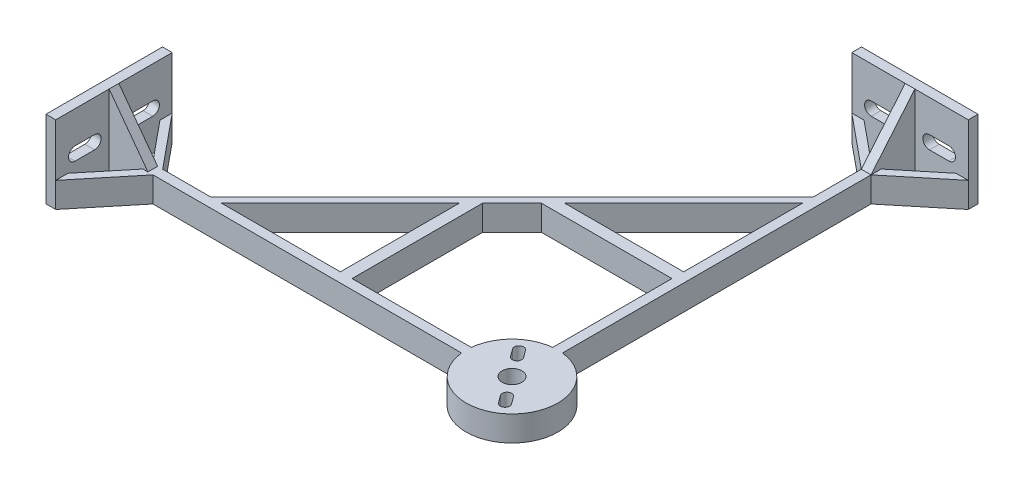
SolidWorks part; units mm, degrees
material "ABS"
ref_plane "Front Plane" through (0, 0, 0) normal (0, 0, 1) x (1, 0, 0)
ref_plane "Top Plane" through (0, 0, 0) normal (0, 1, 0) x (1, 0, 0)
ref_plane "Right Plane" through (0, 0, 0) normal (1, 0, 0) x (0, 0, -1)
sketch "Sketch1" plane through (0, 0, 0) normal (0, 1, 0) x (1, 0, 0)
  line L0 (-1.5875, 14.9158) -> (-1.5875, 130.175)
  line L1 (1.5875, 130.175) -> (1.5875, 14.9158)
  line L2 (-1.5875, 130.175) -> (1.5875, 130.175)
  line L4 (-14.9158, -1.5875) -> (-130.175, -1.5875)
  line L5 (-130.175, -1.5875) -> (-130.175, 1.5875)
  line L8 (-130.175, 1.5875) -> (-14.9158, 1.5875)
  line L9 (0, 0) -> (-130.175, 0) construction
  line L11 (0, 0) -> (0, 146.05) construction
  circle A0 centre (0, 0) radius 15
  point P19 (0, 0)
  point P21 (0, 0)
  dimension "D1" = 30
  dimension "D2" = 3.175
  dimension "D4" = 1.5875
  dimension "D3" = 2
  dimension "D5" = 130.175
extrude "Boss-Extrude2" add sketch "Sketch1" along normal blind 8.255 contours A0
extrude "Boss-Extrude3" add sketch "Sketch1<6>" along normal blind 8.255 contours L4 A0 | A0 | A0 region at (0, 0, -72.5735) region at (-72.5735, 0, 0)
sketch "Sketch1<6>" plane through (0, 0, 0) normal (0, 1, 0) x (1, 0, 0) same geometry as "Sketch1"
sketch "Sketch5" plane through (0, 8.255, 0) normal (0, 1, 0) x (1, 0, 0)
  line L0 (0, 0) -> (130.175, 0) construction
  line L1 (0, 0) -> (0, -22.3627) construction
  line L2 (-6.4967, 8.7797) -> (0, 0) construction
  line L3 (-4.6836, 6.3296) -> (-6.4967, 8.7797) construction
  line L4 (-5.9087, 5.4231) -> (-7.7217, 7.8732)
  line L5 (-3.4586, 7.2361) -> (-5.2716, 9.6862)
  line L6 (0, 0) -> (1.0099, 0.7473) construction
  line L7 (4.6836, -6.3296) -> (6.4967, -8.7797) construction
  line L8 (3.4586, -7.2361) -> (5.2716, -9.6862)
  line L9 (5.9087, -5.4231) -> (7.7217, -7.8732)
  line L10 (-1.5875, 130.175) -> (1.5875, 130.175) construction
  arc A0 (3.4586, -7.2361) -> (5.9087, -5.4231) centre (4.6836, -6.3296) cw
  arc A1 (-5.9087, 5.4231) -> (-3.4586, 7.2361) centre (-4.6836, 6.3296) ccw
  arc A2 (-5.2716, 9.6862) -> (-7.7217, 7.8732) centre (-6.4967, 8.7797) ccw
  arc A3 (7.7217, -7.8732) -> (5.2716, -9.6862) centre (6.4967, -8.7797) cw
  circle A6 centre (0, 0) radius 3.25
  point P8 (-5.5901, 7.5546)
  point P17 (5.5901, -7.5546)
  point P18 (0, 0)
  dimension "D3" = 3.048
  dimension "D1" = 7.874
  dimension "D2" = 3.048
  dimension "D4" = 53.5
extrude "Cut-Extrude3" cut sketch "Sketch5" against normal blind 63.5
ref_axis "Axis1" through (0, 0, 0) along (0, 1, 0)
ref_plane "Plane1" through (0, 0, 0) normal (0, 0, 1) x (1, 0, 0)
ref_plane "Plane2" through (0, 0, 0) normal (1, 0, 0) x (0, 0, -1)
sketch "Sketch7" plane through (0, 0, 0) normal (1, 0, 0) x (0, 0, -1)
  line L1 (130.175, 0) -> (133.35, 0)
  line L2 (130.175, 0) -> (130.175, 25.4)
  line L3 (130.175, 25.4) -> (133.35, 25.4)
  line L4 (133.35, 0) -> (133.35, 25.4)
  dimension "D1" = 3.175
  dimension "D2" = 25.4
extrude "Boss-Extrude5" add sketch "Sketch7" along normal blind 19.05 and the other way blind 19.05
sketch "Sketch8" plane through (-19.05, 0, 0) normal (-1, 0, 0) x (0, 0, 1)
  line L1 (-133.35, 0) -> (-130.175, 0)
  line L2 (-133.35, 0) -> (-133.35, 25.4)
  line L3 (-133.35, 25.4) -> (-130.175, 25.4)
  line L4 (-130.175, 0) -> (-130.175, 25.4)
sketch "Sketch12" plane through (0, 0, -133.35) normal (0, 0, -1) x (-1, 0, 0)
  line L0 (-19.05, 12.7) -> (19.05, 12.7) construction
  line L1 (-19.05, 0) -> (-19.05, 25.4) construction
  line L2 (19.05, 0) -> (19.05, 25.4) construction
  line L3 (-6.35, 12.7) -> (-12.7, 12.7) construction
  line L4 (-6.35, 10.541) -> (-12.7, 10.541)
  line L5 (-6.35, 14.859) -> (-12.7, 14.859)
  line L6 (6.35, 12.7) -> (12.7, 12.7) construction
  line L7 (6.35, 14.859) -> (12.7, 14.859)
  line L8 (6.35, 10.541) -> (12.7, 10.541)
  line L9 (0, 12.7) -> (0, 25.4) construction
  line L10 (19.05, 25.4) -> (-19.05, 25.4) construction
  arc A0 (-6.35, 10.541) -> (-6.35, 14.859) centre (-6.35, 12.7) ccw
  arc A1 (-12.7, 14.859) -> (-12.7, 10.541) centre (-12.7, 12.7) ccw
  arc A2 (6.35, 14.859) -> (6.35, 10.541) centre (6.35, 12.7) ccw
  arc A3 (12.7, 10.541) -> (12.7, 14.859) centre (12.7, 12.7) ccw
  point P8 (-9.525, 12.7)
  point P13 (9.525, 12.7)
  dimension "D1" = 6.35
  dimension "D2" = 4.318
  dimension "D3" = 4.318
  dimension "D4" = 6.35
  dimension "D5" = 9.525
  dimension "D6" = 9.525
extrude "Cut-Extrude6" cut sketch "Sketch12" against normal through all
pattern_circular "CirPattern2" count 2 every 90 about axis through (0, 0, 0) along (0, 1, 0) of "Boss-Extrude5"
pattern_circular "CirPattern3" count 2 every 90 about axis through (0, 0, 0) along (0, 1, 0) of "Cut-Extrude6"
sketch "Sketch13" plane through (0, 0, 0) normal (0, -1, 0) x (1, 0, 0)
  line L0 (-96.6289, -1.5875) -> (-1.5875, -96.6289)
  line L1 (-130.175, -1.5875) -> (-14.9158, -1.5875) construction
  line L2 (-1.5875, -14.9158) -> (-1.5875, -130.175) construction
  line L3 (-100.2211, -1.5875) -> (-1.5875, -100.2211)
  line L4 (-96.6289, -1.5875) -> (-100.2211, -1.5875)
  line L5 (-1.5875, -100.2211) -> (-1.5875, -96.6289)
  line L6 (-19.05, -130.175) -> (-1.5875, -130.175) construction
  line L7 (-130.175, -1.5875) -> (-130.175, -19.05) construction
  line L8 (-19.05, -130.175) -> (-1.5875, -115.8315)
  line L9 (-1.5875, -115.8315) -> (-1.5875, -119.1185)
  line L10 (-1.5875, -119.1185) -> (-15.0482, -130.175)
  line L11 (-15.0482, -130.175) -> (-19.05, -130.175)
  line L12 (19.05, -130.175) -> (1.5875, -115.8315)
  line L13 (1.5875, -130.175) -> (1.5875, -14.9158) construction
  line L14 (1.5875, -115.8315) -> (1.5875, -119.1185)
  line L15 (1.5875, -119.1185) -> (15.0482, -130.175)
  line L16 (1.5875, -130.175) -> (19.05, -130.175) construction
  line L17 (15.0482, -130.175) -> (19.05, -130.175)
  line L18 (-119.1185, 1.5875) -> (-130.175, 15.0482)
  line L19 (-130.175, 19.05) -> (-115.8315, 1.5875)
  line L20 (-130.175, 15.0482) -> (-130.175, 19.05)
  line L21 (-119.1185, -1.5875) -> (-130.175, -15.0482)
  line L22 (-130.175, -19.05) -> (-115.8315, -1.5875)
  line L23 (-115.8315, -1.5875) -> (-119.1185, -1.5875)
  line L24 (-115.8315, 1.5875) -> (-119.1185, 1.5875)
  line L25 (-130.175, -15.0482) -> (-130.175, -19.05)
  point P8 (-1.5875, -72.5454)
  point P9 (-1.5875, -98.425)
  point P12 (-98.425, -1.5875)
  point P25 (-1.5875, -117.475)
  point P30 (1.5875, -117.475)
  point P42 (0, 0)
  dimension "D1" = 31.75
  dimension "D2" = 31.75
  dimension "D3" = 2.54
  dimension "D4" = 2.54
  dimension "D5" = 2.54
  dimension "D6" = 12.7
  dimension "D7" = 2
extrude "Boss-Extrude6" add sketch "Sketch13" against normal up to surface (8.255 mm away) up to face at (0, 8.255, 3.25)
sketch "Sketch14" plane through (0, 0, 0) normal (0, 0, 1) x (1, 0, 0)
  line L0 (-130.175, 25.4) -> (-117.475, 8.255)
  line L1 (-14.9158, 8.255) -> (-115.8315, 8.255) construction
  line L2 (-117.475, 8.255) -> (-130.175, 8.255)
  line L3 (-130.175, 8.255) -> (-130.175, 25.4)
  dimension "D1" = 12.7
extrude "Boss-Extrude7" add sketch "Sketch14" along normal up to surface and the other way up to surface up to face at (-124.6467, 4.1275, 1.5875) other way up to face at (-124.6467, 4.1275, -1.5875)
sketch "Sketch15" plane through (0, 0, 0) normal (1, 0, 0) x (0, 0, -1)
  line L0 (130.175, 25.4) -> (115.8315, 8.255)
  line L1 (115.8315, 8.255) -> (115.8315, 0) construction
  line L2 (130.175, 8.255) -> (115.8315, 8.255) construction
  line L3 (115.8315, 8.255) -> (130.175, 8.255)
  line L4 (130.175, 8.255) -> (130.175, 25.4)
extrude "Boss-Extrude8" add sketch "Sketch15" along normal up to surface and the other way up to surface up to face at (1.5875, 4.1275, -65.3736) other way up to face at (-1.5875, 4.1275, -108.0263)
sketch "Sketch19" plane through (-1.5875, 0, 0) normal (-1, 0, 0) x (0, 0, 1)
  line L0 (-57.7148, 8.255) -> (-57.7148, 0)
  line L1 (-14.9158, 8.255) -> (-96.6289, 8.255) construction
  line L2 (-14.9158, 0) -> (-96.6289, 0) construction
  line L3 (-53.9048, 8.255) -> (-53.9048, 0)
  line L4 (-57.7148, 8.255) -> (-53.9048, 8.255)
  line L5 (-53.9048, 0) -> (-57.7148, 0)
  line L6 (-14.9158, 8.255) -> (-14.9158, 0) construction
  point P10 (-55.8098, 0)
  dimension "D1" = 40.894
  dimension "D2" = 3.81
extrude "Boss-Extrude9" add sketch "Sketch19" along normal up to next
sketch "Sketch20" plane through (0, 0, -1.5875) normal (0, 0, -1) x (-1, 0, 0)
  line L0 (53.9048, 0) -> (53.9048, 8.255)
  line L1 (96.6289, 0) -> (14.9158, 0) construction
  line L2 (96.6289, 8.255) -> (14.9158, 8.255) construction
  line L3 (53.9048, 8.255) -> (57.7148, 8.255)
  line L4 (57.7148, 8.255) -> (57.7148, 0)
  line L5 (53.9048, 0) -> (57.7148, 0)
  line L6 (14.9158, 8.255) -> (14.9158, 0) construction
  point P6 (55.8098, 0)
  dimension "D1" = 40.894
  dimension "D2" = 3.81
extrude "Boss-Extrude10" add sketch "Sketch20" along normal up to next
ref_plane "Plane3" through (-50.0062, 0, -50.0063) normal (-0.7071, 0, -0.7071) x (-0.7071, 0, 0.7071)
